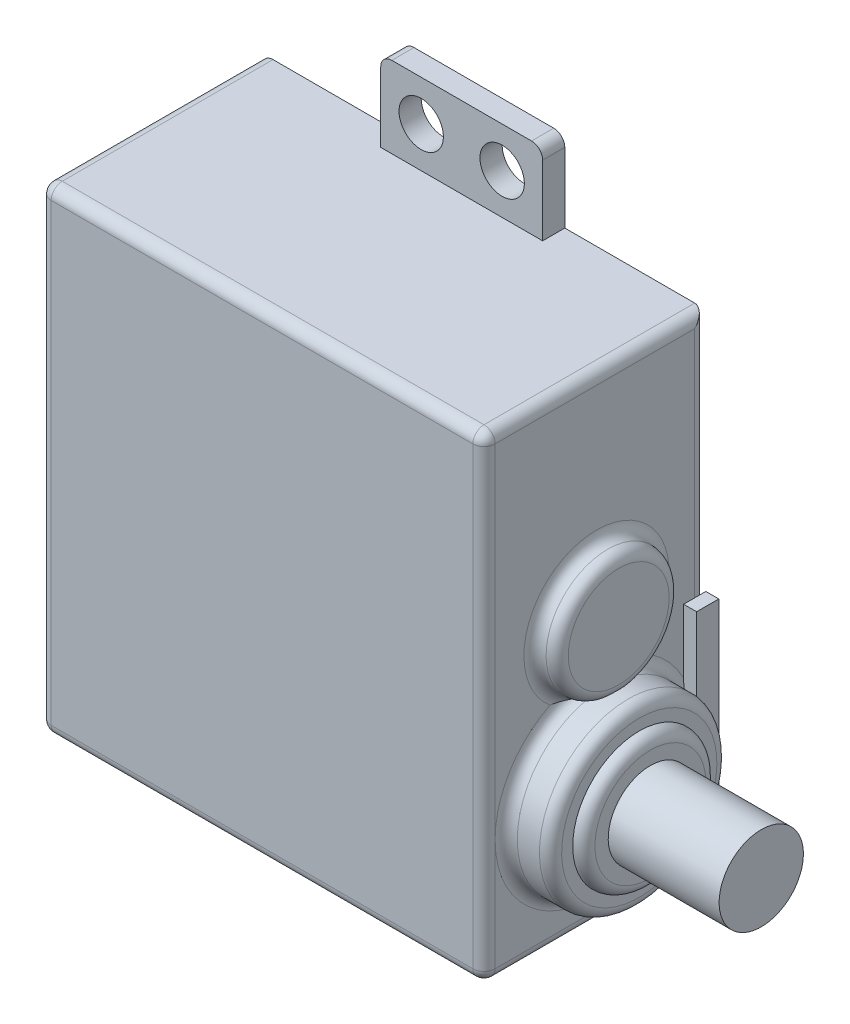
SolidWorks part; units mm, degrees
ref_plane "Front Plane" through (0, 0, 0) normal (0, 0, 1) x (1, 0, 0)
ref_plane "Top Plane" through (0, 0, 0) normal (0, 1, 0) x (1, 0, 0)
ref_plane "Right Plane" through (0, 0, 0) normal (1, 0, 0) x (0, 0, -1)
sketch "Sketch1" plane through (0, 0, 0) normal (0, 0, 1) x (1, 0, 0)
  line L1 (-10.006, 10.7459) -> (10.006, 10.7459)
  line L2 (-10.006, 10.7459) -> (-10.006, -10.7459)
  line L3 (-10.006, -10.7459) -> (10.006, -10.7459)
  line L4 (10.006, 10.7459) -> (10.006, -10.7459)
  line L5 (-10.006, 10.7459) -> (10.006, -10.7459) construction
  line L6 (-10.006, -10.7459) -> (10.006, 10.7459) construction
  point P0 (0, 0)
extrude "Boss-Extrude1" add sketch "Sketch1" along normal blind 10
sketch "Sketch2" plane through (10.006, 0, 0) normal (1, 0, 0) x (0, 0, -1)
  line L0 (-5, -10.7459) -> (-5, 10.7459)
  line L1 (-10, -10.7459) -> (0, -10.7459) construction
  line L2 (-10, 10.7459) -> (0, 10.7459) construction
  line L3 (-10, 0) -> (0, 0)
  line L4 (-10, -10.7459) -> (-10, 10.7459) construction
  circle A0 centre (-5, -5.2111) radius 4
extrude "Boss-Extrude2" add sketch "Sketch2" along normal blind 2 contours L0 A0 | L0 A0 region at (10.006, -5.2111, 6.6977) region at (10.006, -5.2111, 3.3023)
sketch "Sketch3" plane through (10.006, 0, 0) normal (1, 0, 0) x (0, 0, -1)
  circle A0 centre (-4.9265, 1.3238) radius 2.7736
extrude "Boss-Extrude3" add sketch "Sketch3" along normal blind 1
sketch "Sketch4" plane through (12.006, 0, 0) normal (1, 0, 0) x (0, 0, -1)
  circle A0 centre (-5, -5.2111) radius 3
extrude "Boss-Extrude4" add sketch "Sketch4" along normal blind 0.5
sketch "Sketch5" plane through (12.506, 0, 0) normal (1, 0, 0) x (0, 0, -1)
  circle A0 centre (-5, -5.2111) radius 1.9
extrude "Boss-Extrude5" add sketch "Sketch5" along normal blind 5 contours A0
sketch "Sketch6" plane through (0, 0, 0) normal (0, 0, -1) x (-1, 0, 0)
  line L0 (0, 0) -> (-4.3554, 0)
  line L1 (-10.006, 10.7459) -> (10.006, 10.7459) construction
  line L2 (3.6492, 7.0967) -> (-3.6492, 7.0967)
  line L3 (3.6492, 7.0967) -> (3.6492, 14.3951)
  line L4 (3.6492, 14.3951) -> (-3.6492, 14.3951)
  line L5 (-3.6492, 7.0967) -> (-3.6492, 14.3951)
  line L6 (3.6492, 7.0967) -> (-3.6492, 14.3951) construction
  line L7 (3.6492, 14.3951) -> (-3.6492, 7.0967) construction
  line L8 (0, 10.7459) -> (-3.6492, 14.3951)
  line L9 (3.6492, 14.3951) -> (0, 10.7459)
  line L10 (3.6492, -14.3951) -> (-3.6492, -14.3951)
  line L11 (-3.6492, -7.0967) -> (-3.6492, -14.3951)
  line L12 (3.6492, -7.0967) -> (-3.6492, -7.0967)
  line L13 (3.6492, -7.0967) -> (3.6492, -14.3951)
  circle A0 centre (-1.8246, 12.5705) radius 1
  circle A1 centre (1.8246, 12.5705) radius 1
  circle A2 centre (-1.8246, -12.5705) radius 1
  circle A3 centre (1.8246, -12.5705) radius 1
  point P2 (0, 10.7459)
  line M9 (-10.006, -10.7459) -> (10.006, -10.7459)
  line M11 (10.006, 10.7459) -> (-10.006, 10.7459)
extrude "Boss-Extrude6" add sketch "Sketch6" against normal blind 1 contours L13 L11 L10 A2 A3 M9 | A1 L9 L4 L8 A0 | A0 L8 L5 M11 | A1 L9 L3 M11 region at (-1.8246, 10.7975, 0) region at (3.5976, 12.5705, 0) region at (0, 13.2738, 0) region at (0, -12.5705, 0)
sketch "Sketch8" plane through (0, 0, 0) normal (0, 0, -1) x (-1, 0, 0)
  line L0 (-17.506, -5.2111) -> (10.006, -5.2111)
  line L1 (-17.506, -3.3111) -> (-17.506, -7.1111) construction
  line L2 (10.006, 10.7459) -> (10.006, -10.7459) construction
  line L3 (-10.006, -1.2983) -> (-10.006, -9.2111) construction
  line L4 (-10.5913, -10.2461) -> (-9.4207, -10.2461)
  line L5 (-10.5913, -10.2461) -> (-10.5913, -0.2633)
  line L6 (-10.5913, -0.2633) -> (-9.4207, -0.2633)
  line L7 (-9.4207, -10.2461) -> (-9.4207, -0.2633)
  line L8 (-10.5913, -10.2461) -> (-9.4207, -0.2633) construction
  line L9 (-10.5913, -0.2633) -> (-9.4207, -10.2461) construction
  point P6 (-10.006, -5.2547)
  line M5 (-10.006, 10.7459) -> (-10.006, -10.7459)
extrude "Boss-Extrude11" add sketch "Sketch8" against normal blind 1 separate body contours L5 L4 L0 M5 | L6 L5 L0 M5 region at (10.2987, -2.7372, 0) region at (10.2987, -7.7286, 0)
fillet "Fillet1" radius 0.5 2 edges at (-3.6492, 14.3951, 0.5) (3.6492, 14.3951, 0.5)
fillet "Fillet2" radius 0.5 2 edges at (-3.6492, -14.3951, 0.5) (3.6492, -14.3951, 0.5)
fillet "Fillet3" radius 0.5 2 edges at (-10.006, 10.7459, 5) (-10.006, -10.7459, 5)
fillet "Fillet4" radius 0.5 6 edges at (10.006, -10.7459, 5) (10.006, 0, 10) (10.006, 10.7459, 5) (10.006, 0, 0) (10.006, -9.2108, 5.045) (10.006, 4.0972, 4.8952)
fillet "Fillet5" radius 0.5 2 edges at (12.006, -1.2111, 5) (12.506, -2.2111, 5)
fillet "Fillet6" radius 0.5 1 edges at (11.006, 4.0972, 4.8952)
fillet "Fillet7" radius 0.5 7 edges at (9.8596, 10.5994, 9.8536) (9.8596, -10.5994, 9.8536) (-9.8596, -10.5994, 10) (-10.006, 0, 10) (-9.8596, 10.5994, 10) (0, 10.7459, 10) (0, -10.7459, 10)
